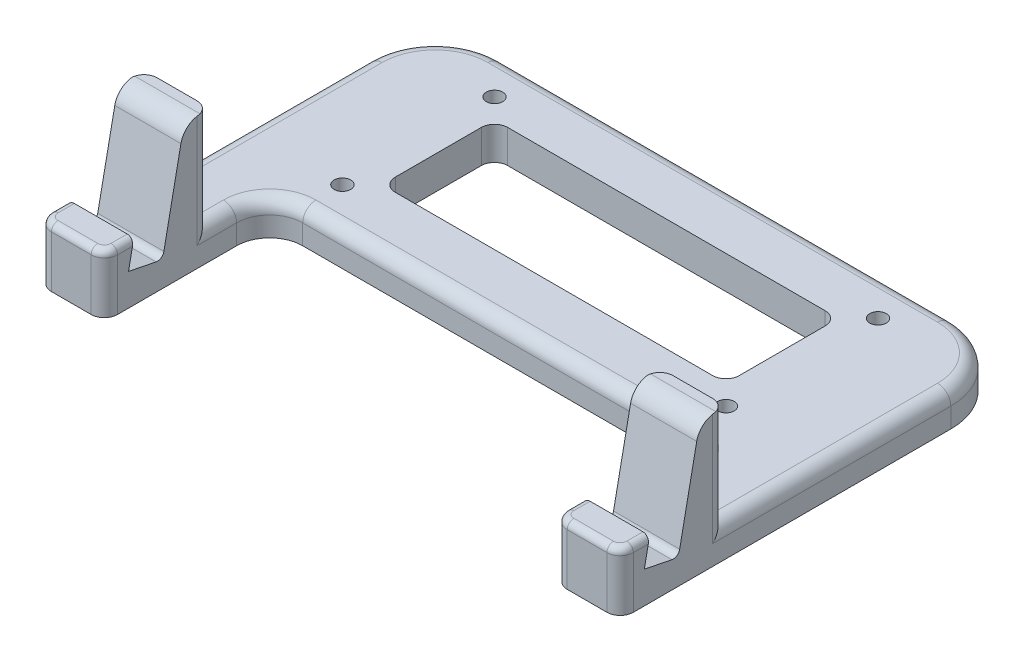
SolidWorks part; units mm, degrees
note: The reader was unsure of these and kept them because the rebuilt part matched: shared geometry of "Sketch1<3>".
material "PE Low/Medium Density"
ref_plane "Front Plane" through (0, 0, 0) normal (0, 0, 1) x (1, 0, 0)
ref_plane "Top Plane" through (0, 0, 0) normal (0, 1, 0) x (1, 0, 0)
ref_plane "Right Plane" through (0, 0, 0) normal (1, 0, 0) x (0, 0, -1)
sketch "Sketch1" plane through (0, 0, 0) normal (0, 1, 0) x (1, 0, 0)
  line L0 (80, -60) -> (86, -60)
  line L1 (10, 0) -> (78, 0)
  line L2 (0, -10) -> (0, -58)
  line L3 (2, -60) -> (8, -60)
  line L4 (88, -10) -> (88, -58)
  line L10 (10, -58) -> (10, -40)
  line L11 (15, -35) -> (73, -35)
  line L12 (78, -58) -> (78, -40)
  line L13 (0, -52) -> (10, -52) construction
  line L14 (15, -6) -> (73, -6) construction
  line L15 (15, -6) -> (15, -29) construction
  line L16 (15, -29) -> (73, -29) construction
  line L17 (73, -6) -> (73, -29) construction
  line L18 (80, -44) -> (86, -44)
  line L19 (2, -44) -> (8, -44)
  line L20 (20, -9) -> (68, -9)
  line L21 (70, -11) -> (70, -24)
  line L22 (20, -26) -> (68, -26)
  line L23 (18, -11) -> (18, -24)
  line L24 (18, -9) -> (18, -26) construction
  line L25 (18, -9) -> (70, -9) construction
  line L26 (18, -26) -> (70, -26) construction
  line L27 (70, -9) -> (70, -26) construction
  arc A0 (0, -10) -> (10, 0) centre (10, -10) cw
  arc A1 (88, -10) -> (78, 0) centre (78, -10) ccw
  arc A2 (0, -58) -> (2, -60) centre (2, -58) ccw
  arc A3 (10, -58) -> (8, -60) centre (8, -58) cw
  arc A4 (86, -60) -> (88, -58) centre (86, -58) ccw
  arc A5 (80, -60) -> (78, -58) centre (80, -58) cw
  arc A6 (15, -35) -> (10, -40) centre (15, -40) ccw
  arc A7 (73, -35) -> (78, -40) centre (73, -40) cw
  circle A8 centre (15, -6) radius 1.25
  circle A9 centre (15, -29) radius 1.25
  circle A10 centre (73, -29) radius 1.25
  circle A11 centre (73, -6) radius 1.25
  arc A12 (86, -44) -> (88, -46) centre (86, -46) cw
  arc A13 (80, -44) -> (78, -46) centre (80, -46) ccw
  arc A14 (10, -46) -> (8, -44) centre (8, -46) ccw
  arc A15 (0, -46) -> (2, -44) centre (2, -46) cw
  arc A16 (18, -11) -> (20, -9) centre (20, -11) cw
  arc A17 (18, -24) -> (20, -26) centre (20, -24) ccw
  arc A18 (70, -11) -> (68, -9) centre (68, -11) ccw
  arc A19 (70, -24) -> (68, -26) centre (68, -24) cw
  point P9 (0, 0)
  point P16 (0, -60)
  point P21 (88, -60)
  dimension "D3" = 10
  dimension "D4" = 10
  dimension "D8" = 2
  dimension "D9" = 2
  dimension "D10" = 2
  dimension "D11" = 2
  dimension "D12" = 5
  dimension "D13" = 5
  dimension "D18" = 2.5
  dimension "D21" = 2
  dimension "D22" = 2
  dimension "D23" = 2
  dimension "D24" = 2
  dimension "D1" = 88
  dimension "D2" = 60
  dimension "D5" = 10
  dimension "D6" = 10
  dimension "D7" = 25
  dimension "D14" = 23
  dimension "D15" = 58
  dimension "D16" = 6
  dimension "D17" = 15
  dimension "D19" = 8
  dimension "D20" = 3
extrude "Boss-Extrude1" add sketch "Sketch1" along normal blind 5 contours L2 A15 L19 A14 L10 A6 L11 A7 L12 A13 L18 A12 L4 A1 L1 A0 A11 A10 A9 A8
extrude "Boss-Extrude2" add sketch "Sketch1<3>" along normal blind 20 contours A15 L2 A2 L3 A3 L10 A14 L19 | L18 A13 L12 A5 L0 A4 L4 A12
sketch "Sketch1<3>" plane through (0, 0, 0) normal (0, 1, 0) x (1, 0, 0) same geometry as "Sketch1"
sketch "Sketch2" plane through (88, 0, 0) normal (1, 0, 0) x (0, 0, -1)
  line L3 (-60, 0) -> (-58, 0) construction
  line L7 (-60, 8.8169) -> (-60, 20)
  line L8 (-60, 20) -> (-47.9372, 20)
  line L9 (-56.3434, 4.8169) -> (-51.1963, 3.7825)
  line L10 (-60, 0) -> (-58, 0)
  line L15 (-51.1963, 3.7825) -> (-47.9372, 20)
  line L16 (-56.3434, 4.8169) -> (-55.5396, 8.8169)
  line L20 (-55.5396, 8.8169) -> (-60, 8.8169)
  dimension "D1" = 5.25
  dimension "D3" = 4
extrude "Cut-Extrude1" cut sketch "Sketch2" against normal through all
fillet "Fillet1" radius 1 10 edges at (0, 8.8169, 56.7698) (10, 8.8169, 56.7698) (9.4142, 8.8169, 59.4142) (5, 8.8169, 60) (0.5858, 8.8169, 59.4142) (78, 8.8169, 56.7698) (78.5858, 8.8169, 59.4142) (88, 8.8169, 56.7698) (87.4142, 8.8169, 59.4142) (83, 8.8169, 60)
fillet "Fillet4" radius 2 5 edges at (88, 5, 28) (85.0711, 5, 2.9289) (44, 5, 0) (2.9289, 5, 2.9289) (0, 5, 28)
fillet "Fillet5" radius 2 5 edges at (10, 5, 43) (11.4645, 5, 36.4645) (78, 5, 43) (76.5355, 5, 36.4645) (44, 5, 35)
fillet "Fillet8" radius 3 2 edges at (83, 20, 47.9372) (5, 20, 47.9372)
fillet "Fillet9" radius 1 2 edges at (83, 3.7825, 51.1963) (5, 3.7825, 51.1963)
